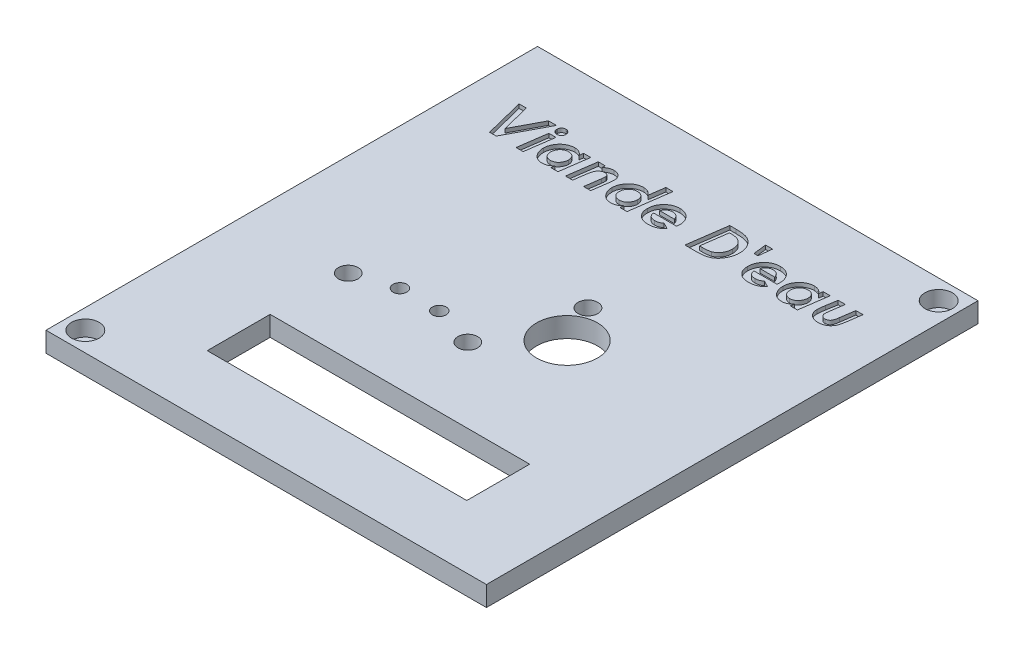
SolidWorks part; units mm, degrees
ref_plane "Front Plane" through (0, 0, 0) normal (0, 0, 1) x (1, 0, 0)
ref_plane "Top Plane" through (0, 0, 0) normal (0, 1, 0) x (1, 0, 0)
ref_plane "Right Plane" through (0, 0, 0) normal (1, 0, 0) x (0, 0, -1)
sketch "Sketch1" plane through (0, 0, 0) normal (0, 1, 0) x (1, 0, 0)
  line L1 (-56, -62.5) -> (56, -62.5)
  line L2 (-56, -62.5) -> (-56, 62.5)
  line L3 (-56, 62.5) -> (56, 62.5)
  line L4 (56, -62.5) -> (56, 62.5)
  line L5 (-56, -62.5) -> (56, 62.5) construction
  line L6 (-56, 62.5) -> (56, -62.5) construction
  point P0 (0, 0)
  dimension "D1" = 112
  dimension "D2" = 125
extrude "Boss-Extrude1" add sketch "Sketch1" along normal blind 5.08
sketch "Sketch5" plane through (0, 5.08, 0) normal (0, 1, 0) x (1, 0, 0)
  line L0 (-56, -62.5) -> (56, -62.5) construction
  line L1 (-31, -46.5) -> (35, -46.5)
  line L2 (-31, -46.5) -> (-31, -30.5)
  line L3 (-31, -30.5) -> (35, -30.5)
  line L4 (35, -46.5) -> (35, -30.5)
  line L5 (-31, -46.5) -> (35, -30.5) construction
  line L6 (-31, -30.5) -> (35, -46.5) construction
  line L10 (-56, 62.5) -> (-56, -62.5) construction
  circle A0 centre (12.5, 1.5) radius 7.75
  circle A1 centre (-30.13, -11.51) radius 2.5
  circle A2 centre (-20.25, -8.2495) radius 1.75
  circle A3 centre (-10.25, -8.2495) radius 1.75
  circle A4 centre (0.2695, -11.51) radius 2.5
  circle A5 centre (8.001, 11.311) radius 2.5
  point P0 (2, -38.5)
  dimension "D4" = 15.5
  dimension "D8" = 5
  dimension "D9" = 3.5
  dimension "D5" = 47.999
  dimension "D6" = 51.189
  dimension "D10" = 43.5
  dimension "D12" = 55.7305
  dimension "D13" = 74.01
  dimension "D14" = 66.25
  dimension "D15" = 70.7495
  dimension "D16" = 70.7495
  dimension "D17" = 76.25
  dimension "D18" = 86.13
  dimension "D19" = 74.01
  dimension "D1" = 66
  dimension "D2" = 16
  dimension "D3" = 16
  dimension "D7" = 25
  dimension "D11" = 61
extrude "Cut-Extrude1" cut sketch "Sketch5" against normal up to next contours A0 | A4 | A3 | A2 | A1 | L1 L4 L3 L2 | A5 region at (2, 5.08, 38.5) region at (12.5, 5.08, -1.5) region at (-30.13, 5.08, 11.51) region at (-20.25, 5.08, 8.2495) region at (-10.25, 5.08, 8.2495) region at (0.2695, 5.08, 11.51) region at (8.001, 5.08, -11.311)
sketch "Sketch7" plane through (0, 5.08, 0) normal (0, 1, 0) x (1, 0, 0)
  line L5 (56, 62.5) -> (-56, 62.5) construction
  line L6 (56, -62.5) -> (56, 62.5) construction
  line L7 (-56, -62.5) -> (56, -62.5) construction
  line L8 (-56, 62.5) -> (-56, -62.5) construction
  circle A0 centre (-51, -57.5) radius 3.5
  circle A1 centre (51, 57.5) radius 3.5
  dimension "D1" = 7
  dimension "D2" = 7
  dimension "D4" = 5
  dimension "D3" = 5
  dimension "D5" = 5
  dimension "D6" = 5
extrude "Cut-Extrude3" cut sketch "Sketch7" against normal blind 4
sketch "Sketch8" plane through (0, 5.08, 0) normal (0, 1, 0) x (1, 0, 0)
  line L0 (-56, 37.5) -> (56, 37.5) construction
  line L1 (56, 62.5) -> (-56, 62.5) construction
  line L2 (-56, 62.5) -> (-56, -62.5) construction
  text T0 "<b><i>Viande D'eau</i></b>" font "Century Gothic" height 10
  point P1 (0, 37.5)
  point P4 (0, 0)
  point P7 (0, 62.5)
  point P8 (0, 0)
  dimension "D1" = 25
extrude "Cut-Extrude4" cut sketch "Sketch8" against normal blind 1
